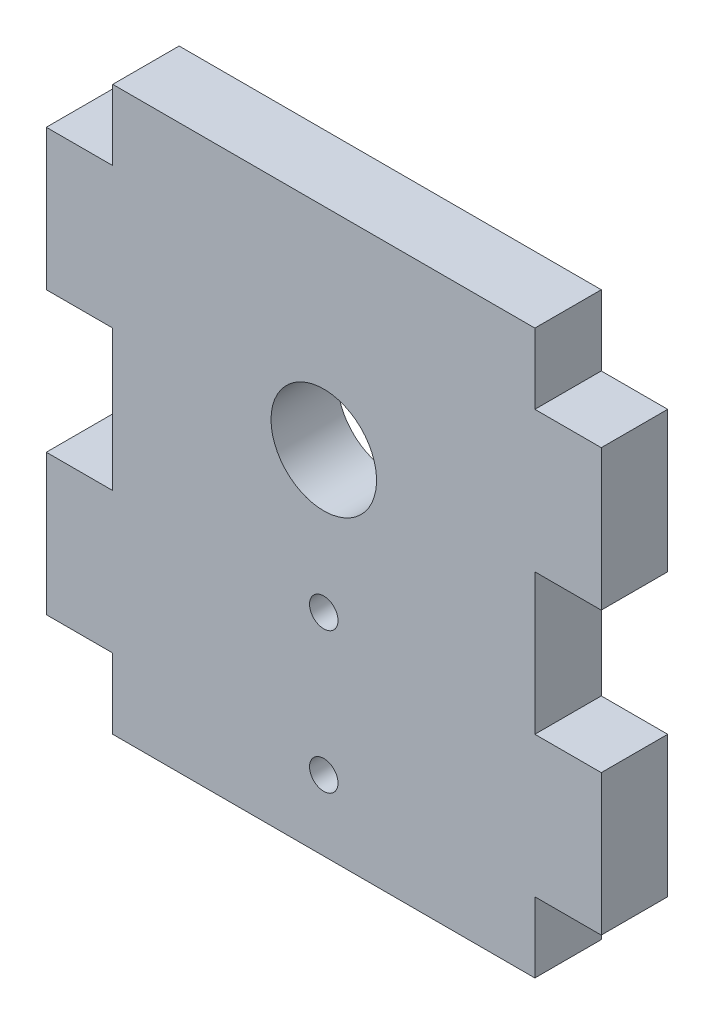
SolidWorks part; units mm, degrees
ref_plane "Front Plane" through (0, 0, 0) normal (0, 0, 1) x (1, 0, 0)
ref_plane "Top Plane" through (0, 0, 0) normal (0, 1, 0) x (1, 0, 0)
ref_plane "Right Plane" through (0, 0, 0) normal (1, 0, 0) x (0, 0, -1)
sketch "Sketch1" plane through (0, 0, 0) normal (0, 0, 1) x (1, 0, 0)
  line L0 (-19.05, 50.8) -> (-19.05, 0) construction
  line L1 (0, 0) -> (-38.1, 0)
  line L2 (0, 0) -> (0, 6.35)
  line L3 (0, 50.8) -> (-38.1, 50.8)
  line L4 (-38.1, 0) -> (-38.1, 6.35)
  line L5 (-38.1, 25.4) -> (0, 25.4) construction
  line L6 (-44.0944, 6.35) -> (-44.0944, 19.05)
  line L7 (-38.1, 44.45) -> (-44.0944, 44.45)
  line L8 (-38.1, 19.05) -> (-38.1, 31.75)
  line L9 (-38.1, 31.75) -> (-44.0944, 31.75)
  line L10 (-44.0944, 44.45) -> (-44.0944, 31.75)
  line L11 (-38.1, 19.05) -> (-44.0944, 19.05)
  line L12 (0, 19.05) -> (0, 31.75)
  line L13 (-38.1, 6.35) -> (-44.0944, 6.35)
  line L14 (0, 6.35) -> (5.9944, 6.35)
  line L15 (0, 44.45) -> (0, 50.8)
  line L16 (0, 19.05) -> (5.9944, 19.05)
  line L17 (5.9944, 44.45) -> (5.9944, 31.75)
  line L18 (0, 31.75) -> (5.9944, 31.75)
  line L20 (0, 44.45) -> (5.9944, 44.45)
  line L21 (5.9944, 6.35) -> (5.9944, 19.05)
  line L22 (-38.1, 44.45) -> (-38.1, 50.8)
  dimension "D1" = 38.1
  dimension "D2" = 50.8
  dimension "D3" = 12.7
  dimension "D4" = 5.9944
  dimension "D5" = 6.35
extrude "Boss-Extrude1" add sketch "Sketch1" along normal blind 5.9944
sketch "Sketch2" plane through (0, 0, 0) normal (0, 0, -1) x (-1, 0, 0)
  line L0 (19.05, 0) -> (19.05, 50.8) construction
  line L1 (38.1, 0) -> (0, 0) construction
  line L2 (0, 50.8) -> (38.1, 50.8) construction
  circle A0 centre (19.05, 31.75) radius 4.7625
  dimension "D1" = 19.05
  dimension "D2" = 9.525
extrude "Cut-Extrude1" cut sketch "Sketch2" against normal through all
sketch "Sketch3" plane through (0, 0, 5.9944) normal (0, 0, 1) x (1, 0, 0)
  circle A0 centre (-19.05, 19.05) radius 1.286
  circle A1 centre (-19.05, 31.75) radius 4.7625 construction
  circle A2 centre (-19.05, 6.35) radius 1.286
  dimension "D1" = 12.7
  dimension "D3" = 2.572
  dimension "D2" = 2
extrude "Cut-Extrude2" cut sketch "Sketch3" against normal through all
